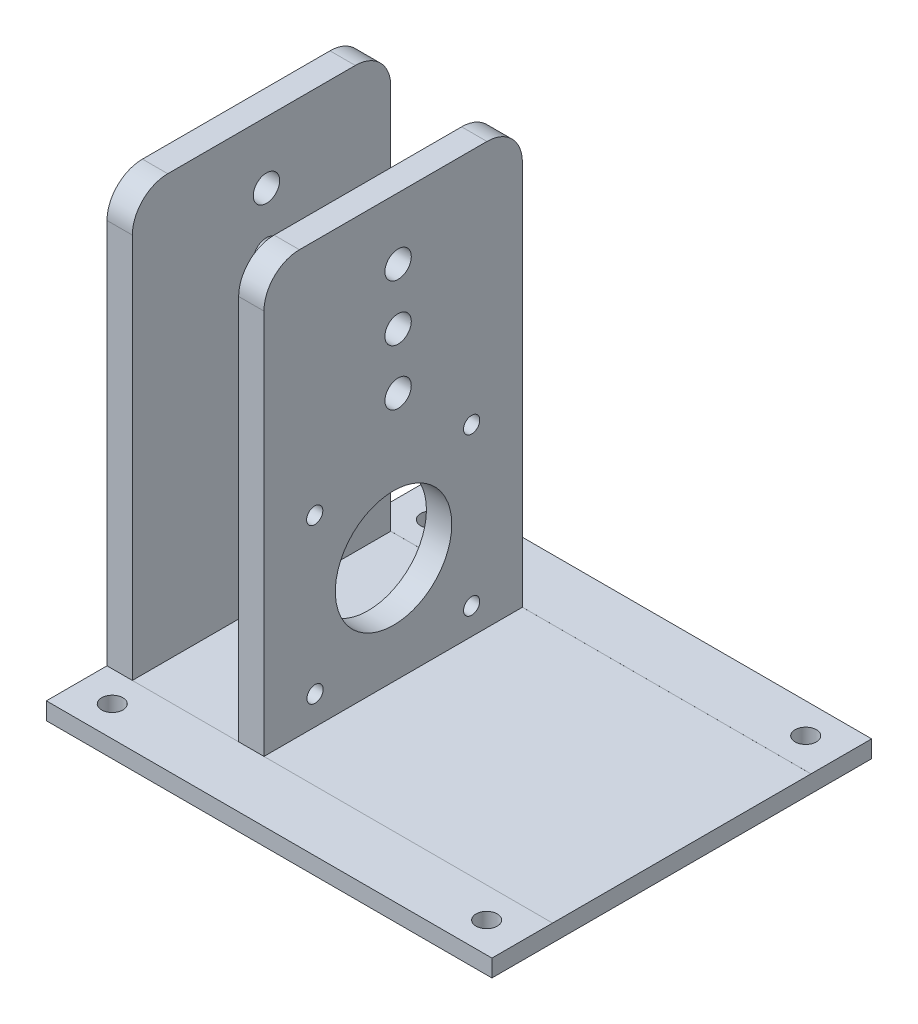
SolidWorks part; units mm, degrees
ref_plane "Front Plane" through (0, 0, 0) normal (0, 0, 1) x (1, 0, 0)
ref_plane "Top Plane" through (0, 0, 0) normal (0, 1, 0) x (1, 0, 0)
ref_plane "Right Plane" through (0, 0, 0) normal (1, 0, 0) x (0, 0, -1)
sketch "Sketch1" plane through (0, 0, 0) normal (0, 1, 0) x (1, 0, 0)
  line L1 (-44.0031, -25.5222) -> (44.0031, -25.5222)
  line L2 (-44.0031, -25.5222) -> (-44.0031, 25.5222)
  line L3 (-44.0031, 25.5222) -> (44.0031, 25.5222)
  line L4 (44.0031, -25.5222) -> (44.0031, 25.5222)
  line L5 (-44.0031, -25.5222) -> (44.0031, 25.5222) construction
  line L6 (-44.0031, 25.5222) -> (44.0031, -25.5222) construction
  point P0 (0, 0)
extrude "Boss-Extrude1" add sketch "Sketch1" along normal blind 3.4061
sketch "Sketch2" plane through (0, 3.4061, 0) normal (0, 1, 0) x (1, 0, 0)
  line L0 (-13.0031, 25.5222) -> (-18.0031, 25.5222)
  line L1 (44.0031, 25.5222) -> (-44.0031, 25.5222) construction
  line L2 (-18.0031, 25.5222) -> (-18.0031, -25.5222)
  line L3 (-44.0031, -25.5222) -> (44.0031, -25.5222) construction
  line L4 (-18.0031, -25.5222) -> (-13.0031, -25.5222)
  line L5 (-13.0031, -25.5222) -> (-13.0031, 25.5222)
  line L6 (-44.0031, 25.5222) -> (-44.0031, -25.5222) construction
  dimension "D1" = 5
  dimension "D2" = 26
extrude "Boss-Extrude3" add sketch "Sketch2" along normal blind 83.1809
sketch "Sketch8" plane through (-13.0031, 0, 0) normal (1, 0, 0) x (0, 0, -1)
  circle A0 centre (0.0714, 24.5561) radius 11.5
extrude "Cut-Extrude3" cut sketch "Sketch8" against normal through all
sketch "Sketch9" plane through (-13.0031, 0, 0) normal (1, 0, 0) x (0, 0, -1)
  circle A0 centre (-15.4286, 9.0561) radius 1.6
  circle A1 centre (-15.5, 39.65) radius 1.6
  circle A2 centre (15.5, 39.65) radius 1.6
  circle A3 centre (15.5, 8.65) radius 1.6
extrude "Cut-Extrude4" cut sketch "Sketch9" against normal through all
sketch "Sketch17" plane through (-44.0031, -0.0607, 0) normal (-1, 0, 0) x (0, 0, 1)
  line L9 (-25.5222, 0.0607) -> (25.5222, 0.0607)
  line L10 (-25.5222, 0.0607) -> (-25.5222, 86.6476)
  line L11 (-25.5222, 86.6476) -> (25.5222, 86.6476)
  line L12 (25.5222, 0.0607) -> (25.5222, 86.6476)
extrude "Boss-Extrude4" add sketch "Sketch17" against normal blind 5
sketch "Sketch20" plane through (-13.0031, 0, 0) normal (1, 0, 0) x (0, 0, -1)
  line L0 (0.9742, 86.587) -> (0.9742, 46.6273) construction
  line L1 (-25.5222, 86.587) -> (25.5222, 86.587) construction
  circle A0 centre (0.9742, 74.3728) radius 2.605
  circle A1 centre (0.9742, 63.2987) radius 2.605
  dimension "5.2" = 5.21
  dimension "D2" = 5.21
extrude "Cut-Extrude6" cut sketch "Sketch20" against normal through all
ref_plane "Plane1" through (-39.0031, 86.587, 25.5222) normal (-1, 0, 0) x (0, 0, 1)
fillet "Fillet2" radius 7 1 edges at (-15.5031, 86.587, 25.5222)
fillet "Fillet4" radius 7 1 edges at (-41.5031, 86.587, 25.5222)
fillet "Fillet5" radius 7 1 edges at (-15.5031, 86.587, -25.5222)
fillet "Fillet6" radius 7 1 edges at (-41.5031, 86.587, -25.5222)
sketch "Sketch21" plane through (-13.0031, 0, 0) normal (1, 0, 0) x (0, 0, -1)
  line L0 (0.9742, 82.8594) -> (0.9742, 45.1185) construction
  line L1 (0.9742, 74.3728) -> (-7.5105, 74.3728) construction
  line L2 (0.9742, 63.2987) -> (-7.5105, 63.2987) construction
  circle A0 centre (0.9742, 52.2987) radius 2.6
  dimension "D1" = 5.2
  dimension "D2" = 11
extrude "Cut-Extrude7" cut sketch "Sketch21" against normal through all
sketch "Sketch23" plane through (-13.0031, 0, 0) normal (1, 0, 0) x (0, 0, -1)
  line L0 (0.9742, 74.3728) -> (-9.1708, 74.3728) construction
  line L1 (0.9742, 63.2987) -> (-9.1708, 63.2987) construction
  line L2 (0.9742, 79.6741) -> (0.9742, 46.4598) construction
  line L3 (0.9742, 52.2987) -> (-9.6651, 52.2987) construction
  dimension "D1" = 11.0741
sketch "Sketch26" plane through (0, 3.4061, 0) normal (0, 1, 0) x (1, 0, 0)
sketch "Sketch27" plane through (0, 0, 0) normal (0, -1, 0) x (1, 0, 0)
  line L0 (44.0031, 25.5222) -> (44.0031, -25.5222) construction
  line L1 (-44.0031, -37.5) -> (44.0031, -37.5)
  line L2 (-44.0031, -37.5) -> (-44.0031, -25.5222)
  line L3 (-44.0031, 37.5) -> (44.0031, 37.5)
  line L4 (44.0031, -37.5) -> (44.0031, -25.5222)
  line L5 (-44.0031, -37.5) -> (0, 0) construction
  line L6 (-44.0031, 37.5) -> (-29.9481, 25.5222) construction
  line L7 (-44.0031, 25.5222) -> (44.0031, 25.5222)
  line L9 (44.0031, -25.5222) -> (-44.0031, -25.5222)
  line L11 (-44.0031, 25.5222) -> (-44.0031, 37.5)
  line L12 (0, 0) -> (44.0031, -37.5) construction
  line L13 (29.9481, 25.5222) -> (44.0031, 37.5) construction
  line L14 (44.0031, 25.5222) -> (44.0031, 37.5)
  point P0 (0, 0)
sketch "Sketch28" plane through (0, 3.4061, 0) normal (0, 1, 0) x (1, 0, 0)
  circle A0 centre (36.9756, 31.5111) radius 2.1
  circle A1 centre (-36.9756, 31.5111) radius 2.1
  circle A2 centre (-36.9756, -31.5111) radius 2.1
  circle A3 centre (36.9756, -31.5111) radius 2.1
extrude "Boss-Extrude7" add sketch "Sketch27" against normal blind 3.41
extrude "Cut-Extrude10" cut sketch "Sketch28" against normal through all both and the other way through all
sketch "Sketch29" plane through (-39.0031, 0, 0) normal (1, 0, 0) x (0, 0, -1)
  line L1 (0.9742, 44.1597) -> (-4.0258, 44.1597)
  line L2 (-4.0258, 44.1597) -> (-4.0258, 47.1597)
  line L3 (-4.0258, 47.1597) -> (5.9742, 47.1597)
  line L4 (5.9742, 47.1597) -> (5.9742, 44.1597)
  line L5 (5.9742, 44.1597) -> (0.9742, 44.1597)
extrude "Boss-Extrude8" add sketch "Sketch29" along normal blind 22
